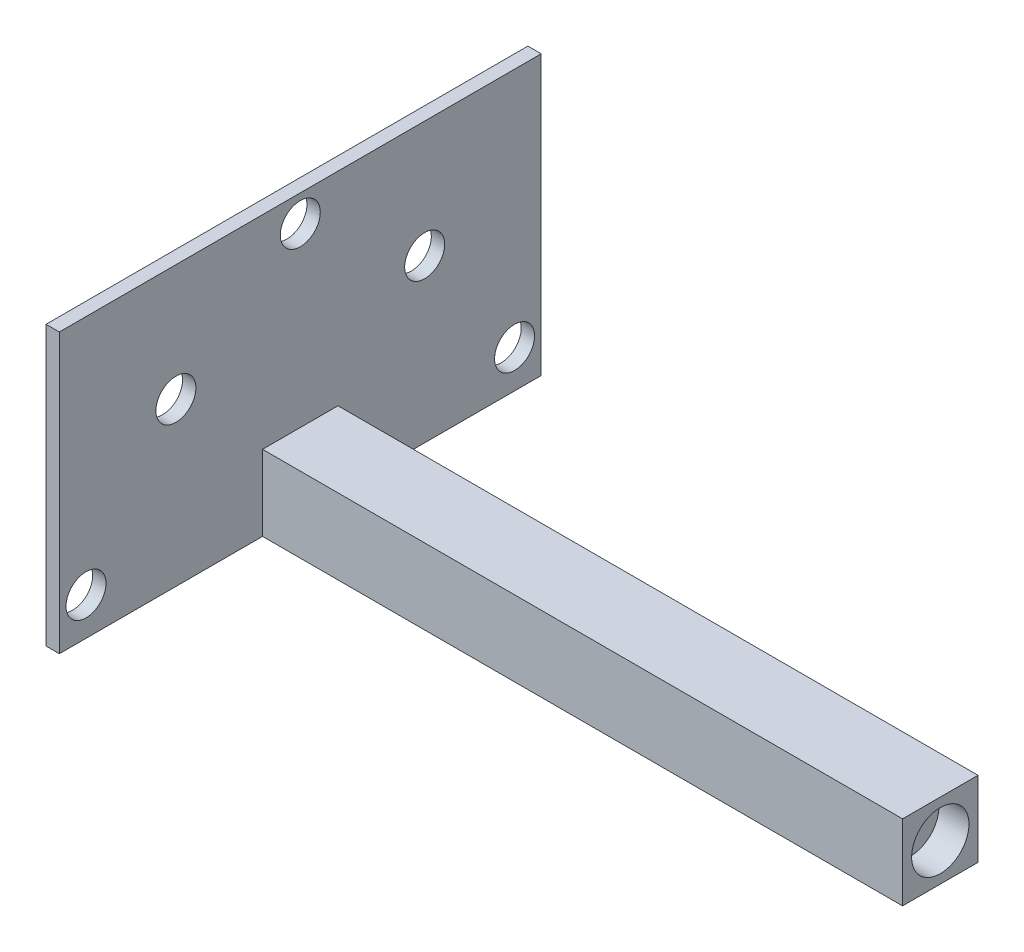
SolidWorks part; units mm, degrees
ref_plane "Front Plane" through (0, 0, 0) normal (0, 0, 1) x (1, 0, 0)
ref_plane "Top Plane" through (0, 0, 0) normal (0, 1, 0) x (1, 0, 0)
ref_plane "Right Plane" through (0, 0, 0) normal (1, 0, 0) x (0, 0, -1)
sketch "Sketch1" plane through (0, 0, 0) normal (1, 0, 0) x (0, 0, -1)
  line L0 (-9.3282, 9.3282) -> (-16.0708, 0) construction
  line L1 (-9.3282, 9.3282) -> (0, 16.0708) construction
  line L3 (-18.0708, -2.8284) -> (18.0708, -2.8284)
  line L4 (-18.0708, -2.8284) -> (-18.0708, 18.0708)
  line L5 (-18.0708, 18.0708) -> (18.0708, 18.0708)
  line L6 (18.0708, -2.8284) -> (18.0708, 18.0708)
  line L7 (-2.8284, -2.8284) -> (2.8284, -2.8284)
  line L8 (-2.8284, -2.8284) -> (-2.8284, 2.8284)
  line L9 (-2.8284, 2.8284) -> (2.8284, 2.8284)
  line L10 (2.8284, -2.8284) -> (2.8284, 2.8284)
  circle A0 centre (0, 0) radius 16.0708 construction
  circle A1 centre (0, 16.0708) radius 1.5
  circle A2 centre (0, 0) radius 16.0708 construction
  circle A3 centre (16.0708, 0) radius 1.5
  circle A4 centre (0, 0) radius 16.0708 construction
  circle A5 centre (0, -16.0708) radius 1.5 construction
  circle A6 centre (0, 0) radius 16.0708 construction
  circle A7 centre (-16.0708, 0) radius 1.5
  circle A8 centre (0, 0) radius 13.1921 construction
  circle A9 centre (-9.3282, 9.3282) radius 1.5
  circle A10 centre (9.3282, 9.3282) radius 1.5
  circle A11 centre (9.3282, -9.3282) radius 1.5 construction
  circle A12 centre (-9.3282, -9.3282) radius 1.5 construction
  circle A13 centre (0, 0) radius 4 construction
  point P16 (0, 0)
  point P27 (0, 0)
  point P34 (0, 0)
  point P35 (0, 0)
  point P36 (0, 0)
  point P37 (0, 0)
  point P38 (0, 0)
  dimension "D1" = 4
  dimension "D2" = 4
  dimension "D3" = 2
  dimension "D6" = 3
  dimension "D7" = 8
  dimension "D4" = 2
  dimension "D5" = 2
extrude "Boss-Extrude1" add sketch "Sketch1" along normal blind 1 contours L3 L6 L5 L4 A10 A9 A7 A3 A1 | L3 L10 L9 L8 region at (0, 8.0104, 0) region at (0, 0, 0)
extrude "Boss-Extrude2" add sketch "Sketch1<3>" along normal blind 49 contours L3 L10 L9 L8 region at (0, 0, 0)
sketch "Sketch1<3>" plane through (0, 0, 0) normal (1, 0, 0) x (0, 0, -1) same geometry as "Sketch1"
sketch "Sketch3" plane through (49, 0, 0) normal (1, 0, 0) x (0, 0, -1)
  circle A1 centre (0, 0) radius 2.15
extrude "Cut-Extrude1" cut sketch "Sketch3" against normal blind 2.25 contours A1
